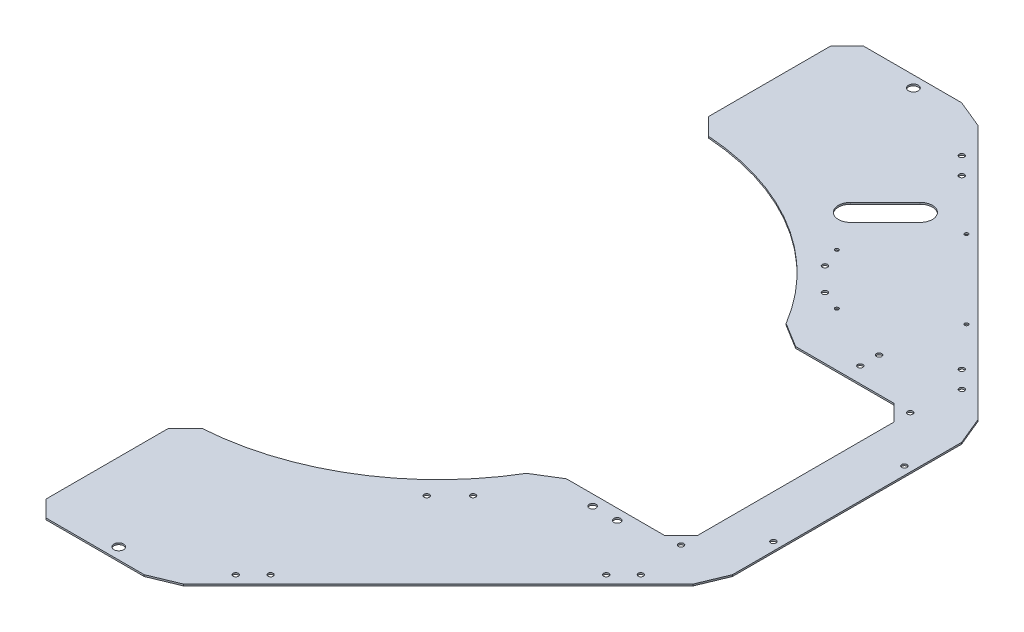
SolidWorks part; units mm, degrees
ref_plane "前视基准面" through (0, 0, 0) normal (0, 0, 1) x (1, 0, 0)
ref_plane "上视基准面" through (0, 0, 0) normal (0, 1, 0) x (1, 0, 0)
ref_plane "右视基准面" through (0, 0, 0) normal (1, 0, 0) x (0, 0, -1)
sketch "草图1" plane through (0, 0, 0) normal (0, 1, 0) x (1, 0, 0)
  line L0 (0, 0) -> (0, 249.7056)
  line L1 (0, 249.7056) -> (80, 249.7056)
  line L2 (80, 249.7056) -> (249.7056, 80)
  line L3 (249.7056, 80) -> (249.7056, 0)
  line L4 (249.7056, 0) -> (249.7056, -80)
  line L5 (249.7056, -80) -> (80, -249.7056)
  line L6 (80, -249.7056) -> (0, -249.7056)
  line L7 (0, -249.7056) -> (0, 0)
  line L8 (0, 0) -> (249.7056, 0) construction
  line L9 (0, 0) -> (164.8528, 164.8528) construction
  line L10 (80, -249.7056) -> (80, 249.7056) construction
  circle A4 centre (0, 0) radius 155
  dimension "D5" = 80
  dimension "D7" = 310
  dimension "D3" = 240
extrude "凸台-拉伸1" add sketch "草图1" along normal blind 1
sketch "草图2" plane through (0, 1, 0) normal (0, 1, 0) x (1, 0, 0)
  line L0 (138.2932, 70) -> (218.2932, 70)
  line L1 (218.2932, 70) -> (218.2932, -70)
  line L2 (218.2932, -70) -> (138.2932, -70)
  line L3 (138.2932, -70) -> (138.2932, 70)
  arc A0 (0, -155) -> (0, 155) centre (0, 0) ccw construction
  dimension "D1" = 140
  dimension "D2" = 80
extrude "切除-拉伸1" cut sketch "草图2" against normal blind 10
chamfer "倒角1" distance 10 12 edges at (0, 0.5, -155) (0, 0.5, -249.7056) (80, 0.5, -249.7056) (249.7056, 0.5, -80) (80, 0.5, 249.7056) (0, 0.5, 249.7056) (0, 0.5, 155) (249.7056, 0.5, 80) (138.2932, 0.5, -70) (138.2932, 0.5, 70) (218.2932, 0.5, 70) (218.2932, 0.5, -70)
sketch "草图3" plane through (0, 1, 0) normal (0, 1, 0) x (1, 0, 0)
  line L0 (164.8528, -164.8528) -> (109.6016, -109.6016) construction
  line L1 (242.6346, -87.0711) -> (87.0711, -242.6346) construction
  line L2 (98.0312, -221.7749) -> (108.6378, -211.1683) construction
  line L3 (103.3345, -216.4716) -> (108.2843, -221.4214) construction
  line L4 (216.4716, -103.3345) -> (221.4214, -108.2843) construction
  line L5 (221.7749, -98.0312) -> (211.1683, -108.6378) construction
  line L6 (0, 0) -> (249.7056, 0) construction
  line L7 (244.7056, -40) -> (249.7056, -40) construction
  line L8 (249.7056, 70) -> (249.7056, -70) construction
  line L9 (244.7056, 40) -> (249.7056, 40) construction
  line L10 (221.7749, 98.0312) -> (211.1683, 108.6378) construction
  line L11 (216.4716, 103.3345) -> (221.4214, 108.2843) construction
  line L12 (103.3345, 216.4716) -> (108.2843, 221.4214) construction
  line L13 (98.0312, 221.7749) -> (108.6378, 211.1683) construction
  line L14 (164.8528, 164.8528) -> (109.6016, 109.6016) construction
  circle A0 centre (98.0312, -221.7749) radius 1.6
  circle A1 centre (108.6378, -211.1683) radius 1.6
  arc A2 (10.3457, -154.6543) -> (133.1879, -79.2843) centre (0, 0) ccw construction
  circle A3 centre (211.1683, -108.6378) radius 1.6
  circle A4 centre (221.7749, -98.0312) radius 1.6
  circle A5 centre (244.7056, -40) radius 1.6
  circle A6 centre (244.7056, 40) radius 1.6
  circle A7 centre (221.7749, 98.0312) radius 1.6
  circle A8 centre (211.1683, 108.6378) radius 1.6
  circle A9 centre (108.6378, 211.1683) radius 1.6
  circle A10 centre (98.0312, 221.7749) radius 1.6
  dimension "D2" = 3.2
  dimension "D6" = 3.2
  dimension "D1" = 15
  dimension "D3" = 7
  dimension "D4" = 80
  dimension "D5" = 5
  dimension "D7" = 40
extrude "切除-拉伸2" cut sketch "草图3" against normal blind 10
sketch "草图4" plane through (0, 1, 0) normal (0, 1, 0) x (1, 0, 0)
  line L0 (170.7932, -76.5) -> (185.7932, -76.5) construction
  line L1 (178.2932, -76.5) -> (178.2932, -70) construction
  line L2 (178.2932, -70) -> (178.2932, 70) construction
  line L3 (148.2932, -70) -> (208.2932, -70) construction
  line L4 (208.2932, 70) -> (148.2932, 70) construction
  line L5 (178.2932, 70) -> (178.2932, 91) construction
  circle A0 centre (170.7932, -76.5) radius 2.1
  circle A1 centre (185.7932, -76.5) radius 2.1
  circle A2 centre (178.2932, 91) radius 1.6
  circle A3 centre (178.2932, 79.5) radius 1.6
  dimension "D1" = 4.2
  dimension "D5" = 3.2
  dimension "D2" = 15
  dimension "D3" = 6.5
  dimension "D4" = 11.5
  dimension "D6" = 9.5
extrude "切除-拉伸3" cut sketch "草图4" against normal blind 10
sketch "草图5" plane through (0, 1, 0) normal (0, 1, 0) x (1, 0, 0)
  line L0 (47.5, 242.75) -> (47.5, -242.75) construction
  line L1 (47.5, 0) -> (0, 0) construction
  circle A0 centre (47.5, -242.75) radius 3
  circle A1 centre (47.5, 242.75) radius 3
  dimension "D1" = 6
  dimension "D2" = 485.5
  dimension "D3" = 47.5
extrude "切除-拉伸4" cut sketch "草图5" against normal blind 10
sketch "草图6" plane through (0, 1, 0) normal (0, 1, 0) x (1, 0, 0)
  line L0 (134.3566, 106.0723) -> (106.0723, 134.3566) construction
  line L1 (106.0723, 134.3566) -> (101.8297, 130.114) construction
  line L2 (101.8297, 130.114) -> (130.114, 101.8297) construction
  line L3 (130.114, 101.8297) -> (134.3566, 106.0723) construction
  line L4 (103.951, 132.2353) -> (132.2353, 103.951) construction
  line L5 (137.8921, 109.6079) -> (109.6079, 137.8921) construction
  line L6 (123.75, 123.75) -> (0, 0) construction
  line L7 (0, 0) -> (249.7056, 0) construction
  line L8 (249.7056, 70) -> (249.7056, -70) construction
  circle A0 centre (128.6997, 107.4865) radius 1.6
  circle A1 centre (114.5576, 121.6287) radius 1.6
  circle A2 centre (128.6997, -107.4865) radius 1.6
  circle A3 centre (114.5576, -121.6287) radius 1.6
  point P11 (120.2145, 120.2145)
  dimension "D4" = 3.2
  dimension "D1" = 45
  dimension "D2" = 40
  dimension "D3" = 6
  dimension "D5" = 5
  dimension "D6" = 5
  dimension "D7" = 20
  dimension "D8" = 40
  dimension "D9" = 175.0089
extrude "切除-拉伸5" cut sketch "草图6" against normal blind 4
sketch "草图7" plane through (0, 1, 0) normal (0, 1, 0) x (1, 0, 0)
  line L0 (218.2932, 70) -> (218.2932, -70) construction
  line L3 (218.2932, 70) -> (213.2932, 65) construction
  line L4 (208.2932, 70) -> (218.2932, 60) construction
  line L5 (218.2932, -60) -> (218.2932, 60) construction
  circle A0 centre (218.2932, 70) radius 1.6
  circle A1 centre (218.2932, -70) radius 1.6
  point P5 (218.2932, 0)
  dimension "D1" = 3.2
extrude "切除-拉伸6" cut sketch "草图7" against normal blind 4
sketch "草图9" plane through (0, 1, 0) normal (0, 1, 0) x (1, 0, 0)
  line L0 (114.5576, 121.6287) -> (128.6997, 107.4865) construction
  line L1 (121.6287, 114.5576) -> (168.3883, 161.3173) construction
  line L2 (87.0711, 242.6346) -> (242.6346, 87.0711) construction
  line L3 (109.6985, 133.7401) -> (140.8112, 102.6274) construction
  line L4 (140.988, 181.6466) -> (188.7177, 133.9169) construction
  line L5 (94.1421, 157.7817) -> (115.3553, 178.9949) construction
  line L6 (88.8388, 163.085) -> (110.052, 184.2983)
  line L7 (99.4454, 152.4784) -> (120.6586, 173.6916)
  circle A0 centre (188.7177, 133.9169) radius 1.1
  circle A1 centre (140.988, 181.6466) radius 1.1
  circle A2 centre (109.6985, 133.7401) radius 1.1
  circle A3 centre (140.8112, 102.6274) radius 1.1
  arc A4 (88.8388, 163.085) -> (99.4454, 152.4784) centre (94.1421, 157.7817) ccw
  arc A5 (120.6586, 173.6916) -> (110.052, 184.2983) centre (115.3553, 178.9949) ccw
  point P10 (125.2548, 118.1838)
  point P13 (164.8528, 157.7817)
  point P20 (104.7487, 168.3883)
  dimension "D4" = 2.2
  dimension "D1" = 67.5
  dimension "D2" = 44
  dimension "D3" = 56
  dimension "D5" = 5
  dimension "D6" = 15
  dimension "D7" = 30
  dimension "D8" = 40
  dimension "D9" = 50
extrude "切除-拉伸7" cut sketch "草图9" against normal blind 10
